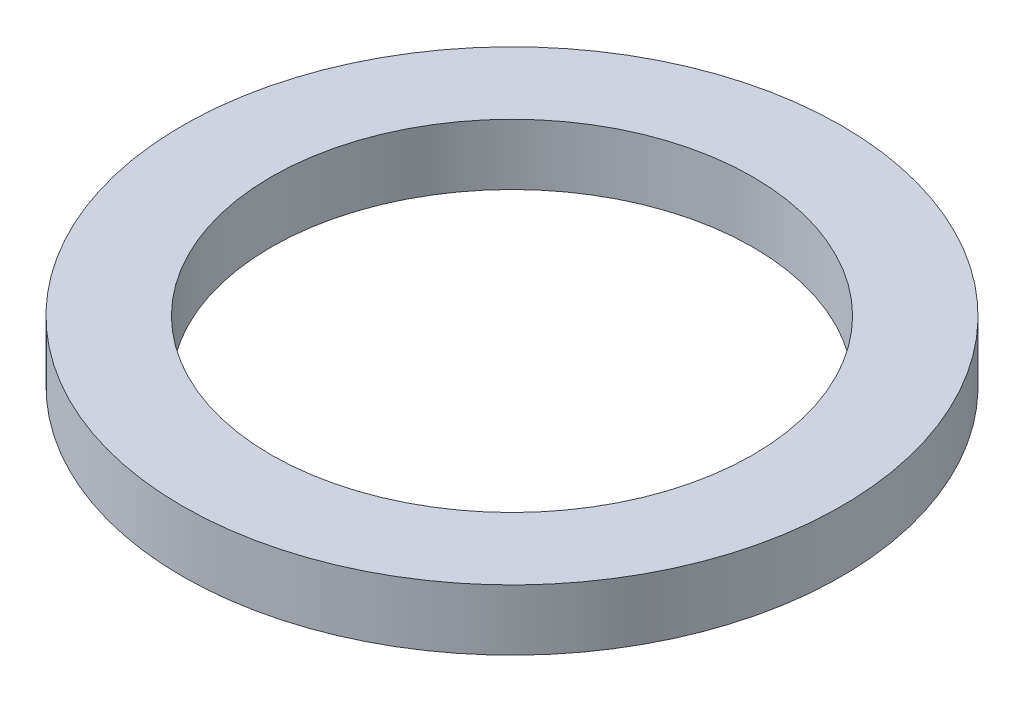
SolidWorks part; units mm, degrees
ref_plane "Front Plane" through (0, 0, 0) normal (0, 0, 1) x (1, 0, 0)
ref_plane "Top Plane" through (0, 0, 0) normal (0, 1, 0) x (1, 0, 0)
ref_plane "Right Plane" through (0, 0, 0) normal (1, 0, 0) x (0, 0, -1)
sketch "Sketch1" plane through (0, 0, 0) normal (0, 1, 0) x (1, 0, 0)
  circle A0 centre (0, 0) radius 65
  dimension "FLANGE_OD" = 130
extrude "Boss-Extrude1" add sketch "Sketch1" along normal blind 12
sketch "Sketch2" plane through (0, 0, 0) normal (0, 1, 0) x (1, 0, 0)
  circle A0 centre (0, 0) radius 47.5
  dimension "BORE_D" = 95
extrude "Cut-Extrude1" cut sketch "Sketch2" along normal through all
sketch "Sketch3" plane through (0, 12, 0) normal (0, 1, 0) x (1, 0, 0)
  circle A0 centre (0, 0) radius 27.4535 construction
  circle A1 centre (-27.4535, 0) radius 2.398
  dimension "BOLT_D" = 4.7959
  dimension "BOLT_PCD" = 54.907
extrude "Cut-Extrude2" cut sketch "Sketch3" against normal blind 10.6761 rebuild error yes
pattern_circular "CirPattern1" count 8 over 360 rebuild error yes
